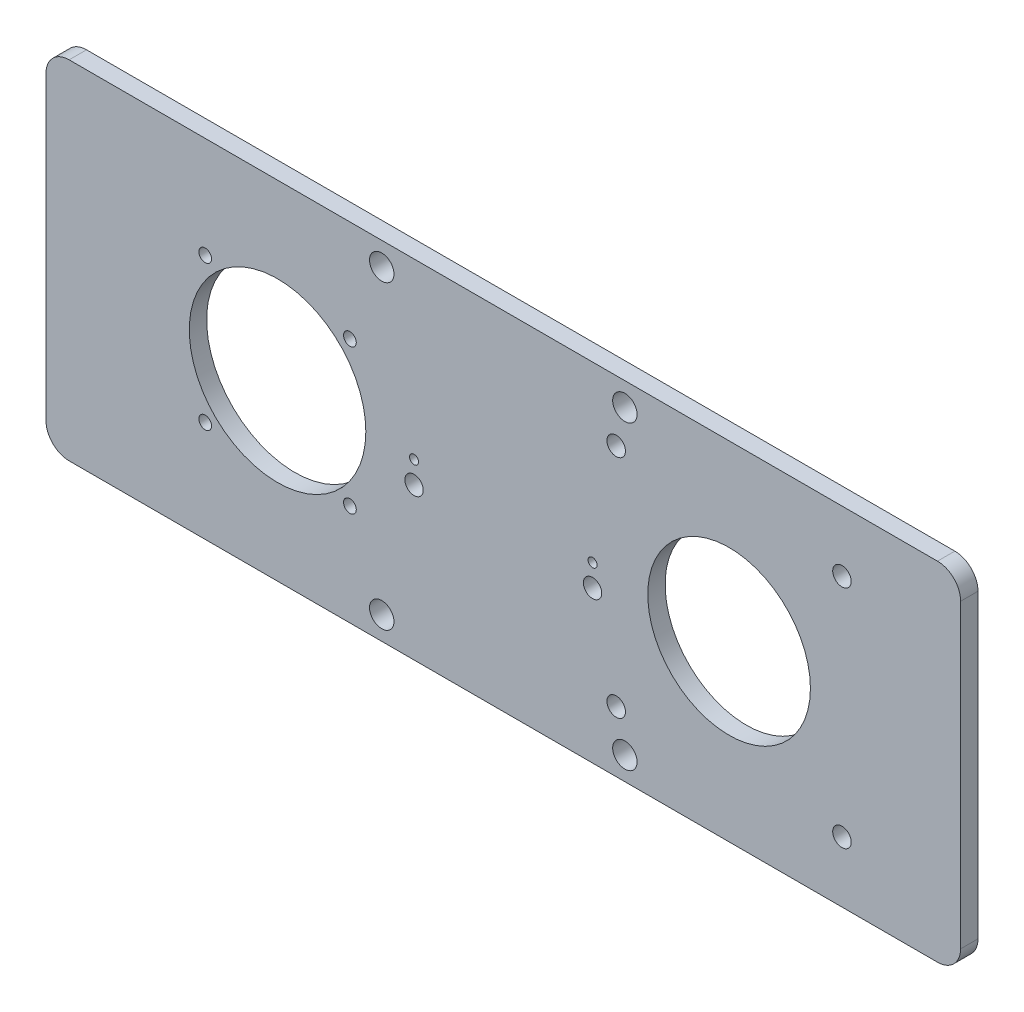
SolidWorks part; units mm, degrees
material "Dragon Plate Carbon Fiber"
ref_plane "Front" through (0, 0, 0) normal (0, 0, 1) x (1, 0, 0)
ref_plane "Top" through (0, 0, 0) normal (0, 1, 0) x (1, 0, 0)
ref_plane "Right" through (0, 0, 0) normal (1, 0, 0) x (0, 0, -1)
sketch "Sketch3" plane through (0, 0, 0) normal (0, 0, 1) x (1, 0, 0)
  line L0 (-69, 0) -> (69, 0) construction
  line L1 (-79, -10) -> (79, -10)
  line L3 (-79, -70) -> (79, -70) construction
  line L5 (-69, 0) -> (-39, 0) construction
  line L6 (-39, 0) -> (39, 0) construction
  line L7 (-39, 0) -> (-39, -40) construction
  line L8 (-39, -40) -> (39, -40) construction
  line L9 (39, -40) -> (39, 0) construction
  line L23 (-79, -10) -> (-79, -70)
  line L24 (-79, -70) -> (79, -70)
  line L25 (79, -70) -> (79, -10)
  line L27 (-21, -14) -> (-21, -66) construction
  line L28 (-51.5, -52.5) -> (-26.5, -52.5) construction
  line L29 (-51.5, -52.5) -> (-51.5, -27.5) construction
  line L30 (-51.5, -27.5) -> (-26.5, -27.5) construction
  line L31 (-26.5, -52.5) -> (-26.5, -27.5) construction
  line L32 (-51.5, -52.5) -> (-26.5, -27.5) construction
  line L33 (-51.5, -27.5) -> (-26.5, -52.5) construction
  line L34 (19.5, -59.5) -> (58.5, -59.5) construction
  line L35 (19.5, -59.5) -> (19.5, -20.5) construction
  line L36 (19.5, -20.5) -> (58.5, -20.5) construction
  line L37 (58.5, -59.5) -> (58.5, -20.5) construction
  line L38 (19.5, -59.5) -> (58.5, -20.5) construction
  line L39 (19.5, -20.5) -> (58.5, -59.5) construction
  line L44 (-21, -66) -> (21, -66) construction
  line L45 (21, -66) -> (21, -14) construction
  line L50 (21, -14) -> (-21, -14) construction
  line L65 (15.4159, -40) -> (15.4159, -43.81) construction
  line L67 (-15.42, -40) -> (-15.42, -43.81) construction
  circle A0 centre (-39, -40) radius 15.25
  circle A1 centre (39, -40) radius 14.05
  point P1 (-79, -40)
  dimension "D8" = 30.5
  dimension "D12" = 28.1
  dimension "D2" = 138
  dimension "D4" = 30
  dimension "D7" = 25
  dimension "D9" = 30.8359
  dimension "D5" = 60
  dimension "D13" = 158
  dimension "D14" = 158
  dimension "D15" = 158
  dimension "D3" = 30
  dimension "D6" = 3.81
  dimension "D10" = 69
  dimension "D11" = 15.42
  dimension "D16" = 39
  dimension "D17" = 79
  dimension "D18" = 10
  dimension "D19" = 4
  dimension "D20" = 4
  dimension "D21" = 58
  dimension "D22" = 58
extrude "Boss-Extrude2" add sketch "Sketch3" against normal blind 3
fillet "Fillet1" radius 4 4 edges at (-79, -70, -1.5) (79, -70, -1.5) (-79, -10, -1.5) (79, -10, -1.5)
sketch "Sketch4" plane through (0, 0, 0) normal (0, 0, 1) x (1, 0, 0)
  point P4 (-51.5, -27.5)
  point P6 (-26.5, -27.5)
  point P8 (-26.5, -52.5)
  point P10 (-51.5, -52.5)
hole_wizard "EVK4-Holes" positions "Sketch4" profile "Sketch6" hole size "Ø1.0" standard "ISO" end condition through all
sketch "Sketch6" plane through (-51.5, -27.5, 0) normal (1, 0, 0) x (0, -1, 0)
  line L0 (0, 0) -> (0, 3)
  line L1 (0, 3) -> (1.1, 3)
  line L2 (1.1, 3) -> (1.1, 0)
  line L5 (1.1, 0) -> (0, 0)
  line L11 (0, -6.35) -> (0, 107.95) construction
  dimension "Thru Hole Dia." = 2.2
  dimension "Thru Hole Depth" = 3
sketch "Sketch7" plane through (0, 0, 0) normal (0, 0, 1) x (1, 0, 0)
  point P0 (19.5, -20.5)
  point P1 (58.5, -20.5)
  point P3 (58.5, -59.5)
  point P5 (19.5, -59.5)
hole_wizard "FLIR-Holes" positions "Sketch7" profile "Sketch8" hole size "Ø1.0" standard "ISO" end condition through all
sketch "Sketch8" plane through (19.5, -20.5, 0) normal (1, 0, 0) x (0, -1, 0)
  line L0 (0, 0) -> (0, 3)
  line L1 (0, 3) -> (1.6, 3)
  line L2 (1.6, 3) -> (1.6, 0)
  line L5 (1.6, 0) -> (0, 0)
  line L11 (0, -6.35) -> (0, 107.95) construction
  dimension "Thru Hole Dia." = 3.2
  dimension "Thru Hole Depth" = 3
sketch "Sketch9" plane through (0, 0, 0) normal (0, 0, 1) x (1, 0, 0)
  point P0 (-15.42, -43.81)
  point P1 (15.4159, -43.81)
hole_wizard "VN-Mount-Holes" positions "Sketch9" profile "Sketch10" hole size "Ø1.0" standard "ISO" end condition through all
sketch "Sketch10" plane through (-15.42, -43.81, 0) normal (1, 0, 0) x (0, -1, 0)
  line L0 (0, 0) -> (0, 3)
  line L1 (0, 3) -> (1.5875, 3)
  line L2 (1.5875, 3) -> (1.5875, 0)
  line L5 (1.5875, 0) -> (0, 0)
  line L11 (0, -6.35) -> (0, 107.95) construction
  dimension "Thru Hole Dia." = 3.175
  dimension "Thru Hole Depth" = 3
sketch "Sketch11" plane through (0, 0, 0) normal (0, 0, 1) x (1, 0, 0)
  point P0 (-15.42, -40)
  point P1 (15.4159, -40)
hole_wizard "VN-Ref-Holes" positions "Sketch11" profile "Sketch12" hole size "Ø1.0" standard "ISO" end condition through all
sketch "Sketch12" plane through (-15.42, -40, 0) normal (1, 0, 0) x (0, -1, 0)
  line L0 (0, 0) -> (0, 3)
  line L1 (0, 3) -> (0.775, 3)
  line L2 (0.775, 3) -> (0.775, 0)
  line L5 (0.775, 0) -> (0, 0)
  line L11 (0, -6.35) -> (0, 107.95) construction
  dimension "Thru Hole Dia." = 1.55
  dimension "Thru Hole Depth" = 3
sketch "Sketch13" plane through (0, 0, 0) normal (0, 0, 1) x (1, 0, 0)
  point P0 (-21, -14)
  point P1 (21, -14)
  point P3 (21, -66)
  point P5 (-21, -66)
hole_wizard "Ø1.0mm Dowel Hole5" positions "Sketch13" profile "Sketch14" hole size "Ø1.0" standard "ISO" end condition through all
sketch "Sketch14" plane through (-21, -14, 0) normal (1, 0, 0) x (0, -1, 0)
  line L0 (0, 0) -> (0, 3)
  line L1 (0, 3) -> (2.11, 3)
  line L2 (2.11, 3) -> (2.11, 0)
  line L5 (2.11, 0) -> (0, 0)
  line L11 (0, -6.35) -> (0, 107.95) construction
  dimension "Thru Hole Dia." = 4.22
  dimension "Thru Hole Depth" = 3
equation "\"M3 Press Fit Nut Diameter\"= 4.22mm"
equation "\"M3 Clearance\"= 3.15mm"
equation "\"CF Thickness\"= 3mm"
equation "\"Tab Clearance\"= 0.1mm"
equation "\"Tab Width\"= 6mm"
equation "\"D10@Sketch3\"=138/2mm"
equation "\"D11@Sketch3\"=30.84/2"
equation "\"D1@Boss-Extrude2\"=\"CF Thickness\""
equation "\"D17@Sketch3\"=158/2mm"
